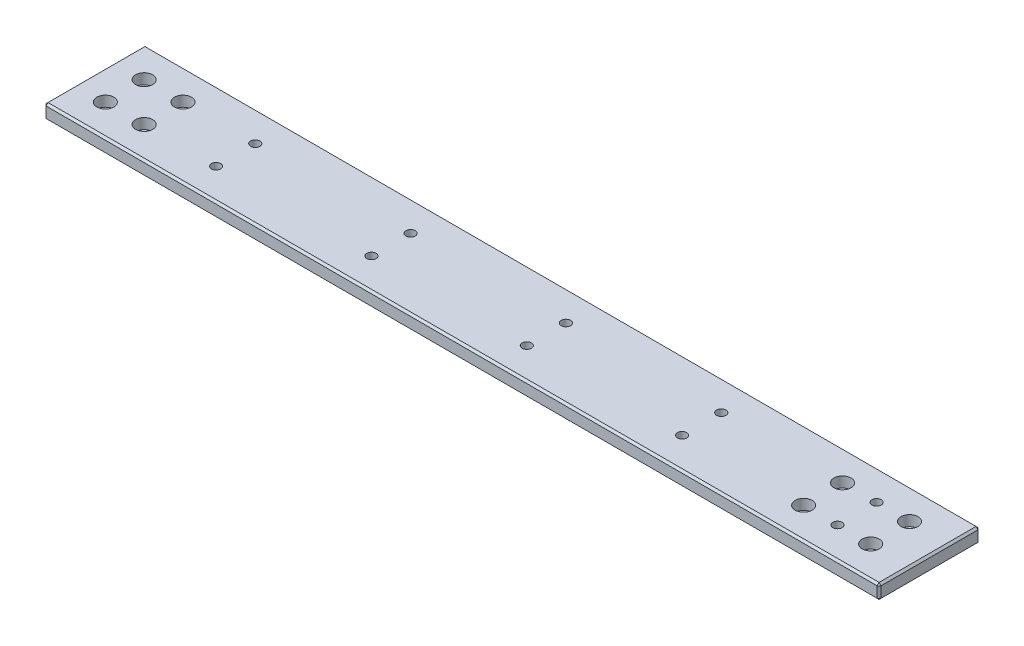
SolidWorks part; units mm, degrees
material "6061 Alloy"
ref_plane "Front" through (0, 0, 0) normal (0, 0, 1) x (1, 0, 0)
ref_plane "Top" through (0, 0, 0) normal (0, 1, 0) x (1, 0, 0)
ref_plane "Right" through (0, 0, 0) normal (1, 0, 0) x (0, 0, -1)
ref_axis "X" through (-80.9, 0, 0) along (1, 0, 0)
ref_axis "Y" through (0, 0, -80.9) along (0, 0, 1)
ref_axis "Z" through (0, 50, 0) along (0, -1, 0)
sketch "Sketch1" plane through (0, 0, 0) normal (0, 1, 0) x (1, 0, 0)
  line L1 (269, 32.5) -> (-269, 32.5)
  line L2 (269, 32.5) -> (269, -32.5)
  line L3 (269, -32.5) -> (-269, -32.5)
  line L4 (-269, 32.5) -> (-269, -32.5)
  line L5 (269, 32.5) -> (-269, -32.5) construction
  line L6 (269, -32.5) -> (-269, 32.5) construction
  point P0 (0, 0)
  dimension "D1" = 65
  dimension "D2" = 538
extrude "Extrude1" add sketch "Sketch1" against normal blind 9.525
hole_wizard "M6x1.0 Tapped Hole1" positions "Sketch3" profile "Sketch2" tap size "M6x1.0" standard "Ansi Metric"
sketch "Sketch3" plane through (0, 0, 0) normal (0, 1, 0) x (-1, 0, 0)
  line L0 (178.0044, 15.9) -> (178.0044, 9.3) construction
  line L1 (175.0044, 15.9) -> (181.0044, 15.9) construction
  line L2 (181.0044, 9.3) -> (175.0044, 9.3) construction
  line L3 (178.0044, -9.3) -> (178.0044, -15.9) construction
  line L4 (175.0044, -9.3) -> (181.0044, -9.3) construction
  line L5 (181.0044, -15.9) -> (175.0044, -15.9) construction
  point P0 (178.0044, 12.6)
  point P1 (178.0044, -12.6)
  point P29 (77.9284, 12.6)
  point P30 (77.9284, -12.6)
  point P31 (-22.1476, 12.6)
  point P32 (-22.1476, -12.6)
  point P33 (-122.2236, 12.6)
  point P34 (-122.2236, -12.6)
  point P35 (-222.2996, 12.6)
  point P36 (-222.2996, -12.6)
sketch "Sketch2" plane through (-178.0044, 0, 12.6) normal (1, 0, 0) x (0, 0, 1)
  line L0 (0, 0) -> (0, 18.4948)
  line L1 (0, 18.4948) -> (2.5, 16.9926)
  line L2 (2.5, 16.9926) -> (2.5, 11.9888)
  line L3 (2.5, 11.9888) -> (3, 11.9888)
  line L4 (3, 11.9888) -> (3, 0)
  line L5 (3, 0) -> (0, 0)
  line L10 (0, 18.4948) -> (-2.5, 16.9926) construction
  line L11 (0, -6.35) -> (0, 107.95) construction
  dimension "Tap Drill Dia." = 5
  dimension "Tap Drill Depth" = 16.9926
  dimension "Thread Major Dia." = 6
  dimension "Thread Depth" = 11.9888
  dimension "Drill Angle" = 118
hole_wizard "CBORE for M6 SHCS1" positions "Sketch5" profile "Sketch4" counterbore size "M6" standard "Ansi Metric" end condition through all
sketch "Sketch5" plane through (0, 0, 0) normal (0, 1, 0) x (-1, 0, 0)
  line L2 (-269, 32.5) -> (-269, -32.5) construction
  point P0 (249.4936, 12.5)
  point P1 (224.4936, 12.5)
  point P4 (224.4936, -12.5)
  point P7 (249.4936, -12.5)
  point P14 (-243.6, 12.5)
  point P16 (-200.42, 12.5)
  point P18 (-243.6, -12.5)
  point P20 (-200.42, -12.5)
  dimension "D1" = 25.4
  dimension "D2" = 43.18
sketch "Sketch4" plane through (-249.4936, 0, 12.5) normal (1, 0, 0) x (0, 0, 1)
  line L0 (0, 0) -> (0, 9.525)
  line L1 (0, 9.525) -> (3.3, 9.525)
  line L3 (3.3, 9.525) -> (3.3, 6.762)
  line L4 (3.3, 6.762) -> (5.5, 6.762)
  line L5 (5.5, 6.762) -> (5.5, 0)
  line L7 (5.5, 0) -> (0, 0)
  line L11 (0, -6.35) -> (0, 107.95) construction
  dimension "Thru Hole Dia." = 6.6
  dimension "Thru Hole Depth" = 9.525
  dimension "C'Bore Dia." = 11
  dimension "C'Bore Depth" = 6.762
chamfer "Chamfer1" distance 1.27 angle 45 12 edges at (-269, -4.7625, -32.5) (-269, -4.7625, 32.5) (-269, 0, 0) (0, 0, 32.5) (0, 0, -32.5) (269, 0, 0) (269, -4.7625, 32.5) (269, -4.7625, -32.5) (0, -9.525, 32.5) (-269, -9.525, 0) (0, -9.525, -32.5) (269, -9.525, 0)
